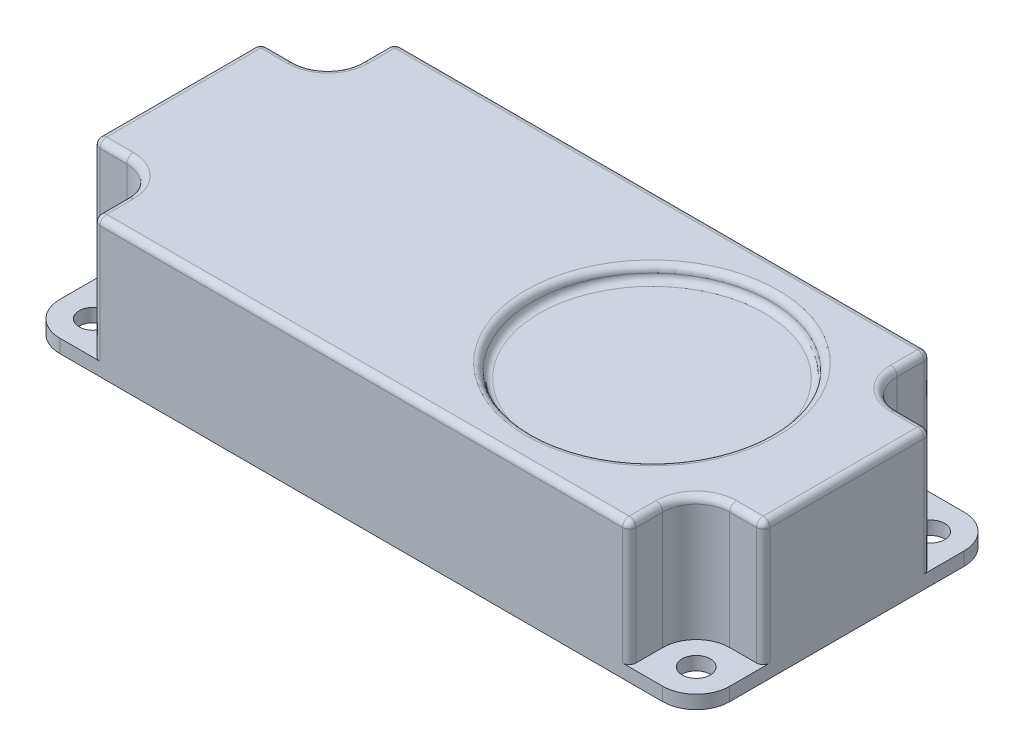
SolidWorks part; units mm, degrees
ref_plane "前视基准面" through (0, 0, 0) normal (0, 0, 1) x (1, 0, 0)
ref_plane "上视基准面" through (0, 0, 0) normal (0, 1, 0) x (1, 0, 0)
ref_plane "右视基准面" through (0, 0, 0) normal (1, 0, 0) x (0, 0, -1)
other "Configuration Table"
sketch "草图1" plane through (0, 0, 0) normal (0, 1, 0) x (1, 0, 0)
  line L1 (-45, -22.5) -> (45, -22.5)
  line L2 (-50, -17.5) -> (-50, 17.5)
  line L3 (-45, 22.5) -> (45, 22.5)
  line L4 (50, -17.5) -> (50, 17.5)
  line L5 (-50, -22.5) -> (50, 22.5) construction
  line L6 (-50, 22.5) -> (50, -22.5) construction
  arc A0 (45, -22.5) -> (50, -17.5) centre (45, -17.5) ccw
  arc A1 (-45, -22.5) -> (-50, -17.5) centre (-45, -17.5) cw
  arc A2 (-50, 17.5) -> (-45, 22.5) centre (-45, 17.5) cw
  arc A3 (45, 22.5) -> (50, 17.5) centre (45, 17.5) cw
  point P0 (0, 0)
  dimension "D3" = 5
  dimension "D1" = 100
  dimension "D2" = 45
extrude "凸台-拉伸1" add sketch "草图1" along normal blind 2 contours L4 A3 L3 A2 L2 A1 L1 A0
sketch "草图2" plane through (0, 2, 0) normal (0, 1, 0) x (1, 0, 0)
  line L0 (-40, 22.5) -> (-40, 17.5)
  line L1 (-40, -22.5) -> (40, -22.5)
  line L2 (-50, -12.5) -> (-50, 12.5)
  line L3 (-40, 22.5) -> (40, 22.5)
  line L4 (50, -12.5) -> (50, 12.5)
  line L7 (40, 22.5) -> (40, 17.5)
  line L8 (-50, 12.5) -> (-45, 12.5)
  line L9 (50, -12.5) -> (45, -12.5)
  line L10 (40, -17.5) -> (40, -22.5)
  line L11 (45, 12.5) -> (50, 12.5)
  line L14 (-40, -17.5) -> (-40, -22.5)
  line L15 (-45, -12.5) -> (-50, -12.5)
  arc A0 (40, 17.5) -> (45, 12.5) centre (45, 17.5) ccw
  arc A1 (45, -12.5) -> (40, -17.5) centre (45, -17.5) ccw
  arc A2 (-40, -17.5) -> (-45, -12.5) centre (-45, -17.5) ccw
  arc A3 (-45, 12.5) -> (-40, 17.5) centre (-45, 17.5) ccw
  point P0 (0, 0)
extrude "凸台-拉伸3" add sketch "草图2" along normal blind 18.5
fillet "圆角1" radius 1 24 edges at (47.5, 20.5, -12.5) (50, 20.5, 0) (47.5, 20.5, 12.5) (41.4645, 20.5, 13.9645) (40, 20.5, 20) (0, 20.5, 22.5) (-40, 20.5, 20) (-41.4645, 20.5, 13.9645) (-47.5, 20.5, 12.5) (-50, 20.5, 0) (-47.5, 20.5, -12.5) (-41.4645, 20.5, -13.9645) (-40, 20.5, -20) (0, 20.5, -22.5) (40, 20.5, -20) (41.4645, 20.5, -13.9645) (50, 11.25, -12.5) (40, 11.25, -22.5) (-40, 11.25, -22.5) (-50, 11.25, -12.5) (-40, 11.25, 22.5) (-50, 11.25, 12.5) (40, 11.25, 22.5) (50, 11.25, 12.5)
sketch "草图4" plane through (0, 20.5, 0) normal (0, 1, 0) x (1, 0, 0)
  circle A0 centre (20.8924, 0) radius 17.8213
extrude "切除-拉伸1" cut sketch "草图4" against normal blind 2
fillet "圆角2" radius 1 2 edges at (20.8924, 18.5, 17.8213) (20.8924, 20.5, 17.8213)
sketch "草图5" plane through (0, 2, 0) normal (0, 1, 0) x (1, 0, 0)
  circle A0 centre (-45, 17.5) radius 2.1
  circle A1 centre (45, 17.5) radius 2.1
  circle A2 centre (45, -17.5) radius 2.1
  circle A3 centre (-45, -17.5) radius 2.1
  point P14 (-60.1879, 5.7301)
  dimension "D1" = 4.2
  dimension "D2" = 4.2
  dimension "D3" = 4.2
  dimension "D4" = 4.2
  dimension "D5" = 90
  dimension "D6" = 35
extrude "切除-拉伸2" cut sketch "草图5" against normal blind 2
